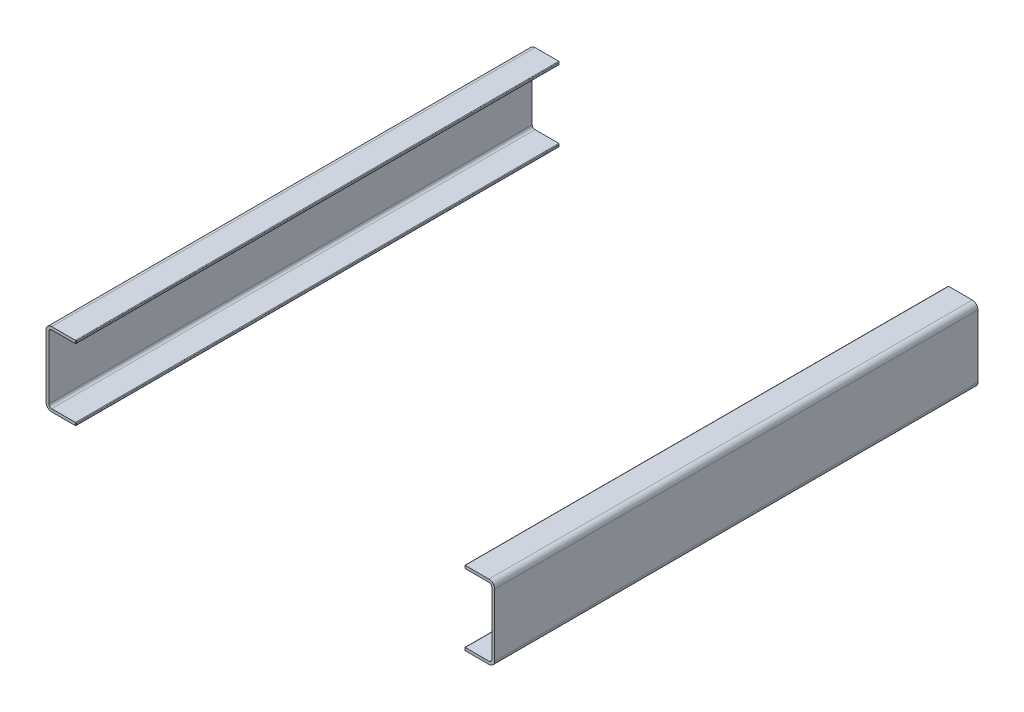
SolidWorks part; units mm, degrees
ref_plane "Front Plane" through (0, 0, 0) normal (0, 0, 1) x (1, 0, 0)
ref_plane "Top Plane" through (0, 0, 0) normal (0, 1, 0) x (1, 0, 0)
ref_plane "Right Plane" through (0, 0, 0) normal (1, 0, 0) x (0, 0, -1)
ref_plane "Plane2" through (123, 0, 0) normal (-1, 0, 0) x (0, 0, 1)
sketch "Sketch6" plane through (123, 0, 0) normal (-1, 0, 0) x (0, 0, 1)
  line L0 (153, 23.4) -> (-153, 23.4)
  line L1 (-153, 23.4) -> (-153, -23.4)
  line L2 (-153, -23.4) -> (153, -23.4)
  line L3 (153, -23.4) -> (153, 23.4)
  line L4 (0, -23.4) -> (0, 0) construction
  line L5 (-153, 0) -> (0, 0) construction
  line L6 (0, 0) -> (153, 0) construction
  line L7 (0, 0) -> (0, 23.4) construction
  dimension "D1" = 306
  dimension "D2" = 46.8
extrude "Boss-Extrude2" add sketch "Sketch6" against normal blind 19 separate body
sketch "Sketch7" plane through (0, 0, 153) normal (0, 0, 1) x (1, 0, 0)
  line L0 (123, -21.6) -> (140.2, -21.6)
  line L1 (140.2, -21.6) -> (140.2, 21.6)
  line L2 (140.2, 21.6) -> (123, 21.6)
  line L3 (123, 21.6) -> (123, -21.6)
extrude "Cut-Extrude2" cut sketch "Sketch7" against normal through all
fillet "Fillet4" radius 0.4 8 edges at (123, -22.5, -153) (123, -21.6, 0) (123, -23.4, 0) (123, -22.5, 153) (123, 21.6, 0) (123, 22.5, 153) (123, 22.5, -153) (123, 23.4, 0)
fillet "Fillet5" radius 1.8 2 edges at (140.2, 21.6, 0) (140.2, -21.6, 0) tangent propagation no
fillet "Fillet6" radius 3.6 2 edges at (142, -23.4, 0) (142, 23.4, 0) tangent propagation no
ref_plane "Plane3" through (-123, 0, 0) normal (1, 0, 0) x (0, 0, -1)
sketch "Sketch12" plane through (-123, 0, 0) normal (1, 0, 0) x (0, 0, -1)
  line L0 (-153, 23.4) -> (-153, -23.4)
  line L1 (-153, -23.4) -> (153, -23.4)
  line L2 (153, -23.4) -> (153, 23.4)
  line L3 (153, 23.4) -> (-153, 23.4)
  line L4 (-153, -23.4) -> (-153, 23.4) construction
  line L5 (153, 23.4) -> (153, -23.4) construction
  line L6 (153, -23.4) -> (-153, -23.4) construction
  line L7 (-153, 23.4) -> (153, 23.4) construction
extrude "Boss-Extrude3" add sketch "Sketch12" against normal blind 19 separate body
sketch "Sketch13" plane through (0, 0, 153) normal (0, 0, 1) x (1, 0, 0)
  line L0 (-123, -21.6) -> (-123, 21.6)
  line L1 (-123, 21.6) -> (-140.2, 21.6)
  line L2 (-140.2, 21.6) -> (-140.2, -21.6)
  line L3 (-140.2, -21.6) -> (-123, -21.6)
extrude "Cut-Extrude3" cut sketch "Sketch13" against normal through all
fillet "Fillet7" radius 0.4 8 edges at (-123, 23.4, 0) (-123, 22.5, 153) (-123, 22.5, -153) (-123, 21.6, 0) (-123, -22.5, -153) (-123, -23.4, 0) (-123, -22.5, 153) (-123, -21.6, 0)
fillet "Fillet8" radius 1.8 2 edges at (-140.2, 21.6, 0) (-140.2, -21.6, 0) tangent propagation no
fillet "Fillet9" radius 3.6 2 edges at (-142, -23.4, 0) (-142, 23.4, 0) tangent propagation no
